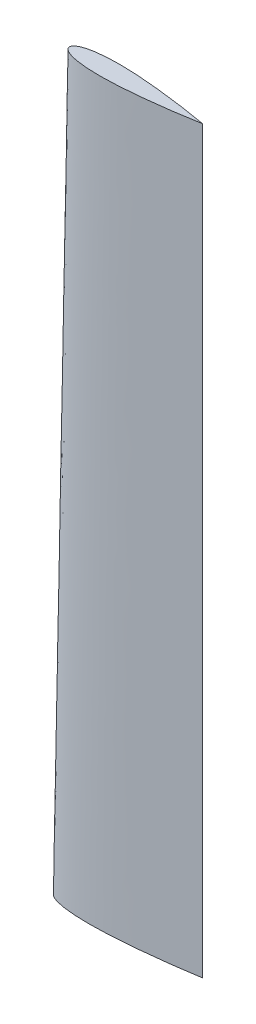
SolidWorks part; units mm, degrees
ref_plane "Front Plane" through (0, 0, 0) normal (0, 0, 1) x (1, 0, 0)
ref_plane "Top Plane" through (0, 0, 0) normal (0, 1, 0) x (1, 0, 0)
ref_plane "Right Plane" through (0, 0, 0) normal (1, 0, 0) x (0, 0, -1)
sketch "Sketch2" plane through (0, 0, 0) normal (0, 1, 0) x (1, 0, 0)
  line L1 (0, 0) -> (500, 0)
  spline S0 degree 4 poles (0, 0) (-0.0001, 0.4669) (0.0459, 1.2052) (0.2186, 2.2603) (0.6399, 3.618) (1.1941, 4.8728) (2.0121, 6.2579) (3.1905, 7.8075) (4.9161, 9.597) (7.5082, 11.7259) (11.5334, 14.3231) (17.851, 17.4646) (27.9215, 21.2183) (43.6731, 25.4125) (67.356, 29.5728) (98.0153, 32.5808) (133.8908, 33.9799) (167.7974, 33.7908) (196.8403, 32.8478) (221.0243, 31.6357) (240.3587, 30.4435) (259.68, 29.0541) (278.9879, 27.4897) (298.2821, 25.7676) (317.5634, 23.9019) (336.8305, 21.9036) (356.0858, 19.7805) (375.3248, 17.5383) (394.5546, 15.1788) (411.3603, 13.0139) (425.7676, 11.0826) (437.7475, 9.4259) (447.3616, 8.0641) (456.9012, 6.6821) (466.5619, 5.2471) (475.9952, 3.815) (484.6111, 2.4718) (491.3905, 1.3966) (498.4667, 0.2523) (502.8156, -0.46) (509.8471, -1.6256) (515.3712, -2.563) (522.0701, -3.7103) (528.0423, -4.757) (534.4731, -5.8975) (540.5786, -7.0041) (545.364, -7.8827) (548.4208, -8.4534) (550.0042, -8.7494) knots 0 0 0 0 0 0.003309 0.005259 0.007569 0.010082 0.013037 0.016668 0.021375 0.027713 0.036828 0.050647 0.07143 0.103979 0.152532 0.221375 0.290217 0.35906 0.393481 0.427902 0.462324 0.496745 0.531166 0.565587 0.600009 0.63443 0.668851 0.703273 0.737694 0.772115 0.789326 0.806536 0.823747 0.840958 0.858168 0.875379 0.892589 0.901195 0.9098 0.921075 0.93235 0.943625 0.9549 0.966175 0.97745 0.988725 1 1 1 1 1 construction
  spline S1 degree 4 poles (0, 0) (-0.0001, 0.4669) (0.0459, 1.2052) (0.2186, 2.2603) (0.6399, 3.618) (1.1941, 4.8728) (2.0121, 6.2579) (3.1905, 7.8075) (4.9161, 9.597) (7.5082, 11.7259) (11.5334, 14.3231) (17.851, 17.4646) (27.9215, 21.2183) (43.6731, 25.4125) (67.356, 29.5728) (98.0153, 32.5808) (133.8908, 33.9799) (167.7974, 33.7908) (196.8403, 32.8478) (221.0243, 31.6357) (240.3587, 30.4435) (259.68, 29.0541) (278.9879, 27.4897) (298.2821, 25.7676) (317.5634, 23.9019) (336.8305, 21.9036) (356.0858, 19.7805) (375.3248, 17.5383) (394.5546, 15.1788) (411.3603, 13.0139) (425.7676, 11.0826) (437.7475, 9.4259) (447.3616, 8.0641) (456.9012, 6.6821) (466.5619, 5.2471) (475.9952, 3.815) (484.6111, 2.4718) (491.3905, 1.3966) (496.7207, 0.5346) (498.913, 0.1778) (500, 0) knots 0 0 0 0 0 0.003309 0.005259 0.007569 0.010082 0.013037 0.016668 0.021375 0.027713 0.036828 0.050647 0.07143 0.103979 0.152532 0.221375 0.290217 0.35906 0.393481 0.427902 0.462324 0.496745 0.531166 0.565587 0.600009 0.63443 0.668851 0.703273 0.737694 0.772115 0.789326 0.806536 0.823747 0.840958 0.858168 0.875379 0.892589 0.901195 0.9098 0.9098 0.9098 0.9098 0.9098
ref_plane "Plane1" through (0, 2500, 0) normal (0, 1, 0) x (1, 0, 0)
sketch "Sketch3" plane through (0, 2500, 0) normal (0, 1, 0) x (1, 0, 0)
  line L0 (49.9973, 0) -> (499.9973, 0)
  spline S0 degree 4 poles (49.9973, 0) (49.9971, 0.4896) (50.0437, 1.281) (50.2229, 2.4252) (50.6703, 3.9134) (51.2699, 5.2951) (52.148, 6.8017) (53.3927, 8.4595) (55.1825, 10.345) (57.8361, 12.5638) (61.8572, 15.2128) (67.9821, 18.3384) (77.4798, 21.9984) (91.7365, 25.9503) (112.9584, 29.8815) (140.3303, 32.7157) (167.9335, 33.8283) (193.9807, 33.8246) (220.0161, 33.1534) (241.6957, 32.1144) (263.3523, 30.6906) (284.9847, 28.9447) (302.2759, 27.3763) (319.5521, 25.6531) (336.8141, 23.7888) (351.9048, 22.0436) (364.8318, 20.4708) (375.596, 19.1109) (384.2072, 17.9932) (394.9588, 16.5614) (407.8669, 14.7834) (422.8906, 12.6299) (440.0824, 10.0457) (455.0548, 7.6894) (467.9583, 5.5762) (478.5698, 3.7844) (486.2279, 2.4577) (492.3132, 1.385) (498.6355, 0.249) (502.5421, -0.462) (508.8626, -1.6261) (513.8363, -2.5639) (519.8649, -3.7112) (525.2413, -4.7582) (531.0266, -5.8983) (536.5231, -7.0051) (540.8245, -7.8827) (543.5787, -8.4539) (545.0002, -8.7492) knots 0 0 0 0 0 0.003841 0.006235 0.009072 0.012193 0.015657 0.019917 0.025339 0.032593 0.042799 0.057705 0.079311 0.112503 0.158973 0.227236 0.2955 0.329632 0.363764 0.432028 0.46616 0.500292 0.534424 0.568556 0.602688 0.63682 0.653886 0.670952 0.688018 0.705084 0.739215 0.773347 0.807479 0.841611 0.858677 0.875743 0.892809 0.901342 0.909875 0.921141 0.932406 0.943672 0.954938 0.966203 0.977469 0.988734 1 1 1 1 1 construction
  spline S1 degree 4 poles (49.9973, 0) (49.9971, 0.4896) (50.0437, 1.281) (50.2229, 2.4252) (50.6703, 3.9134) (51.2699, 5.2951) (52.148, 6.8017) (53.3927, 8.4595) (55.1825, 10.345) (57.8361, 12.5638) (61.8572, 15.2128) (67.9821, 18.3384) (77.4798, 21.9984) (91.7365, 25.9503) (112.9584, 29.8815) (140.3303, 32.7157) (167.9335, 33.8283) (193.9807, 33.8246) (220.0161, 33.1534) (241.6957, 32.1144) (263.3523, 30.6906) (284.9847, 28.9447) (302.2759, 27.3763) (319.5521, 25.6531) (336.8141, 23.7888) (351.9048, 22.0436) (364.8318, 20.4708) (375.596, 19.1109) (384.2072, 17.9932) (394.9588, 16.5614) (407.8669, 14.7834) (422.8906, 12.6299) (440.0824, 10.0457) (455.0548, 7.6894) (467.9583, 5.5762) (478.5698, 3.7844) (486.2279, 2.4577) (492.3132, 1.385) (497.0666, 0.5309) (499.0258, 0.1765) (499.9973, 0) knots 0 0 0 0 0 0.003841 0.006235 0.009072 0.012193 0.015657 0.019917 0.025339 0.032593 0.042799 0.057705 0.079311 0.112503 0.158973 0.227236 0.2955 0.329632 0.363764 0.432028 0.46616 0.500292 0.534424 0.568556 0.602688 0.63682 0.653886 0.670952 0.688018 0.705084 0.739215 0.773347 0.807479 0.841611 0.858677 0.875743 0.892809 0.901342 0.909875 0.909875 0.909875 0.909875 0.909875
loft "Loft1" add profiles "Sketch2", "Sketch3" connector at (0, 0, 0) connector at (49.9973, 2500, 0)
mirror "Mirror1" about plane through (0, 0, 0) normal (0, 0, 1) of "Loft1"
ref_plane "Plane2" through (500, 0, 0) normal (1, 0, 0) x (0, 0, -1)
equation "\"chord\"= 0.5'Root chord length"
equation "\"maxThickness\"= 0.15'Naca symmetric airfoil last two digits divided by 100"
equation "\"aspectRatio\"= 5'Aspect ratio"
equation "\"taperRatio\"= 0.9'Taper ratio of horizontal stabilizer"
equation "\"sweepAngle\" = 1.1457'Leading edge sweep angle"
equation "\"D1@Plane1\"=\"chord\"*\"aspectRatio\""
equation "\"D1@Plane2\"=1*\"chord\""
